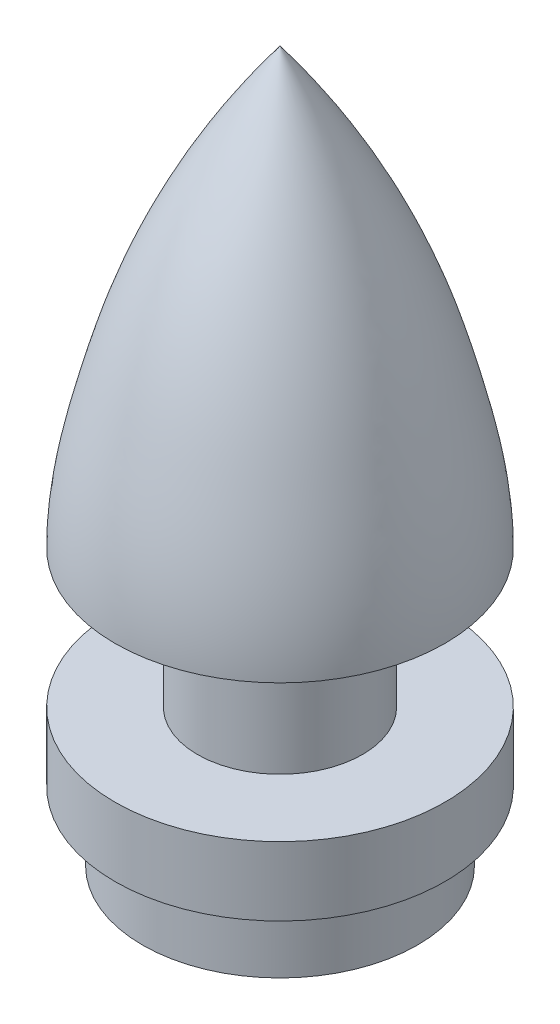
SolidWorks part; units mm, degrees
ref_plane "前基準面" through (0, 0, 0) normal (0, 0, 1) x (1, 0, 0)
ref_plane "上基準面" through (0, 0, 0) normal (0, 1, 0) x (1, 0, 0)
ref_plane "右基準面" through (0, 0, 0) normal (1, 0, 0) x (0, 0, -1)
sketch "草圖1" plane through (0, 0, 0) normal (0, 0, 1) x (1, 0, 0)
  line L0 (0, 61.3742) -> (0, -20.2778) construction
  line L1 (0, 0) -> (5, 0)
  line L2 (5, 0) -> (5, 2.5)
  line L3 (5, 2.5) -> (6, 2.5)
  line L4 (6, 2.5) -> (6, 5)
  line L5 (0, 25.8137) -> (0, 0)
  line L6 (6, 5) -> (3, 5)
  line L7 (3, 5) -> (3, 10)
  line L8 (3, 10) -> (6, 10)
  spline S0 degree 3 poles (6, 10) (6, 11.7901) (5.4733, 14.0832) (3.9611, 19.5012) (2.1079, 22.9996) (0, 25.8137) knots 0 0 0 0 0.308621 0.408621 1 1 1 1
  dimension "D1" = 3
  dimension "D2" = 5
  dimension "D3" = 5
  dimension "D4" = 5
  dimension "D5" = 1
  dimension "D6" = 2.5
revolve "旋轉1" add sketch "草圖1" angle 360 about L0
sketch "草圖2" plane through (0, 0, 0) normal (0, -1, 0) x (1, 0, 0)
  circle A0 centre (0, 0) radius 1.5
  dimension "D1" = 3
extrude "除料-伸長1" cut sketch "草圖2" against normal blind 8
